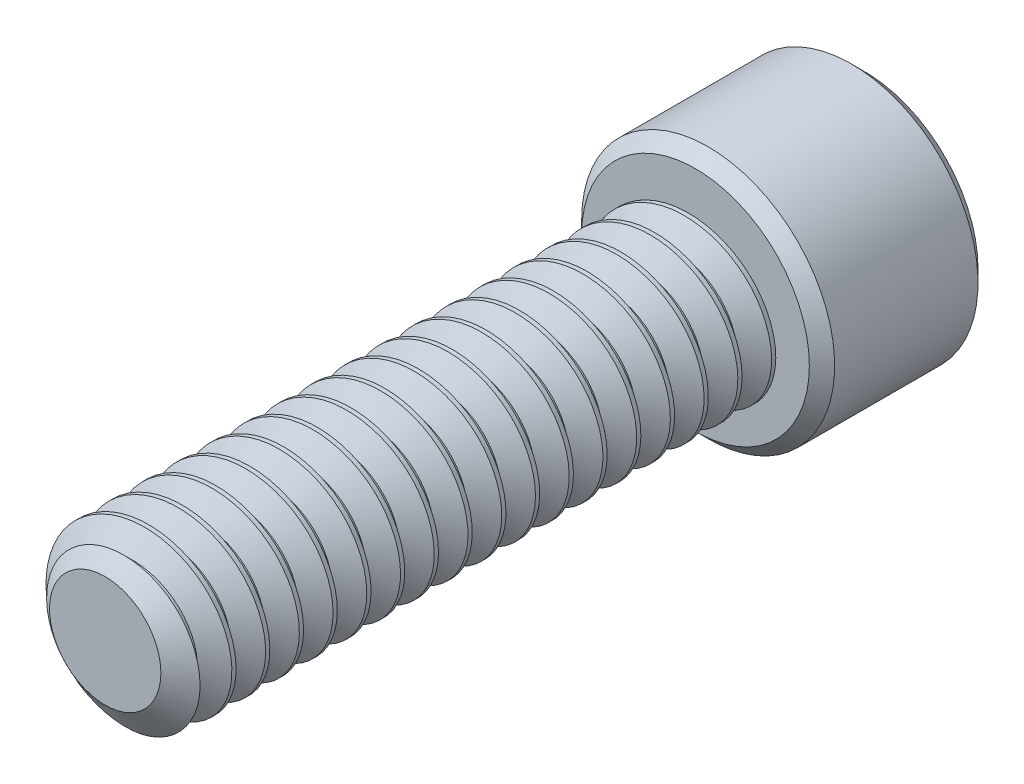
SolidWorks part; units mm, degrees
other "DetailItem1"
ref_plane "Front Plane" through (0, 0, 0) normal (0, 0, 1) x (1, 0, 0)
ref_plane "Top Plane" through (0, 0, 0) normal (0, 1, 0) x (1, 0, 0)
ref_plane "Right Plane" through (0, 0, 0) normal (1, 0, 0) x (0, 0, -1)
sketch "Sketch1" plane through (0, 0, 0) normal (0, 0, 1) x (1, 0, 0)
  circle A0 centre (0, 0) radius 3.175
  dimension "OD" = 6.35
extrude "Extrude1" add sketch "Sketch1" against normal blind 22.225
sketch "Sketch2" plane through (0, 0, 0) normal (0, 0, 1) x (1, 0, 0)
  circle A0 centre (0, 0) radius 3.175 construction
  circle A1 centre (0, 0) radius 3.175
curve "Helix/Spiral1" pitch 1.27 height 23.495 turns 18.5 parameters "pitch"=1.27
sketch "Sketch3" plane through (0, 0, 0) normal (1, 0, 0) x (0, 0, -1)
  line L0 (-1.1112, 3.175) -> (-0.635, 2.3501)
  line L1 (-0.635, 2.3501) -> (-0.4763, 2.3501)
  line L2 (-0.4763, 2.3501) -> (0, 3.175)
  line L3 (-1.1112, 3.175) -> (0, 3.175)
  line L4 (-0.5556, 3.175) -> (-0.5556, 2.3501) construction
  line L5 (-0.8731, 2.7626) -> (-0.2381, 2.7626) construction
  line L6 (0, 3.175) -> (0, -3.175) construction
  dimension "D1" = 0.1588
  dimension "D2" = 0.635
  dimension "D3" = 60
sweep "Cut-Sweep1" cut profiles "Sketch3" path "Helix/Spiral1"
sketch "Sketch4" plane through (0, 0, 0) normal (1, 0, 0) x (0, 0, -1)
  line L0 (0.7554, 3.175) -> (0, 2.0961)
  line L1 (0, 2.0961) -> (0, 3.175)
  line L2 (0.7554, 3.175) -> (0, 3.175)
  line L3 (-1.1112, 3.175) -> (0, 3.175) construction
  line L4 (0, 0) -> (7.0209, 0) construction
  dimension "D1" = 55
  dimension "D2" = 0.254
revolve "Cut-Revolve1" cut sketch "Sketch4" angle 360 about L4
sketch "Sketch6" plane through (0, 0, -22.225) normal (0, 0, -1) x (-1, 0, 0)
  circle A0 centre (0, 0) radius 4.7625
  dimension "head dia" = 9.525
extrude "Extrude2" add sketch "Sketch6" along normal blind 6.35
sketch "Sketch7" plane through (0, 0, -28.575) normal (0, 0, -1) x (-1, 0, 0)
  line L1 (0, 2.7496) -> (-2.3813, 1.3748)
  line L2 (-2.3813, 1.3748) -> (-2.3813, -1.3748)
  line L3 (-2.3813, -1.3748) -> (0, -2.7496)
  line L4 (0, -2.7496) -> (2.3813, -1.3748)
  line L5 (2.3813, -1.3748) -> (2.3813, 1.3748)
  line L6 (2.3813, 1.3748) -> (0, 2.7496)
  circle A0 centre (0, 0) radius 2.3813 construction
  dimension "hex dia" = 4.7625
extrude "Cut-Extrude1" cut sketch "Sketch7" against normal blind 3.5719
sketch "Sketch8" plane through (0, 0, -28.575) normal (0, 0, -1) x (-1, 0, 0)
  circle A0 centre (0, 0) radius 2.7496
extrude "Cut-Extrude2" cut sketch "Sketch8" against normal through all draft 45
chamfer "Chamfer1" distance 0.4763 angle 45 2 edges at (-4.7625, 0, -28.575) (-4.7625, 0, -22.225)
sketch "Sketch10" plane through (0, 0, -22.225) normal (0, 0, 1) x (1, 0, 0)
  circle A0 centre (0, 0) radius 3.175
extrude "Partial Thread" [suppressed] add sketch "Sketch10" along normal offset from surface (25.4 mm away) 22.225
sketch "Sketch9" plane through (0, 0, 0) normal (1, 0, 0) x (0, 0, -1)
  line L0 (0, 3.175) -> (0, -3.175) construction
  line L1 (1.905, 3.175) -> (1.905, -3.175) construction
  dimension "D1" = 1.905
equation "\"D3@Helix/Spiral1\" = \"screw length@Extrude1\"+\"pitch@Helix/Spiral1\""
equation "\"D1@Sketch3\" = \"pitch@Helix/Spiral1\"*.125"
equation "\"D2@Sketch3\" = \"pitch@Helix/Spiral1\"*.5"
equation "\"D1@Cut-Extrude1\" = \"hex dia@Sketch7\"*.75"
equation "\"D1@Chamfer1\" = \"head dia@Sketch6\"*.05"
equation "\"D1@Sketch9\" = \"pitch@Helix/Spiral1\"*1.5"
